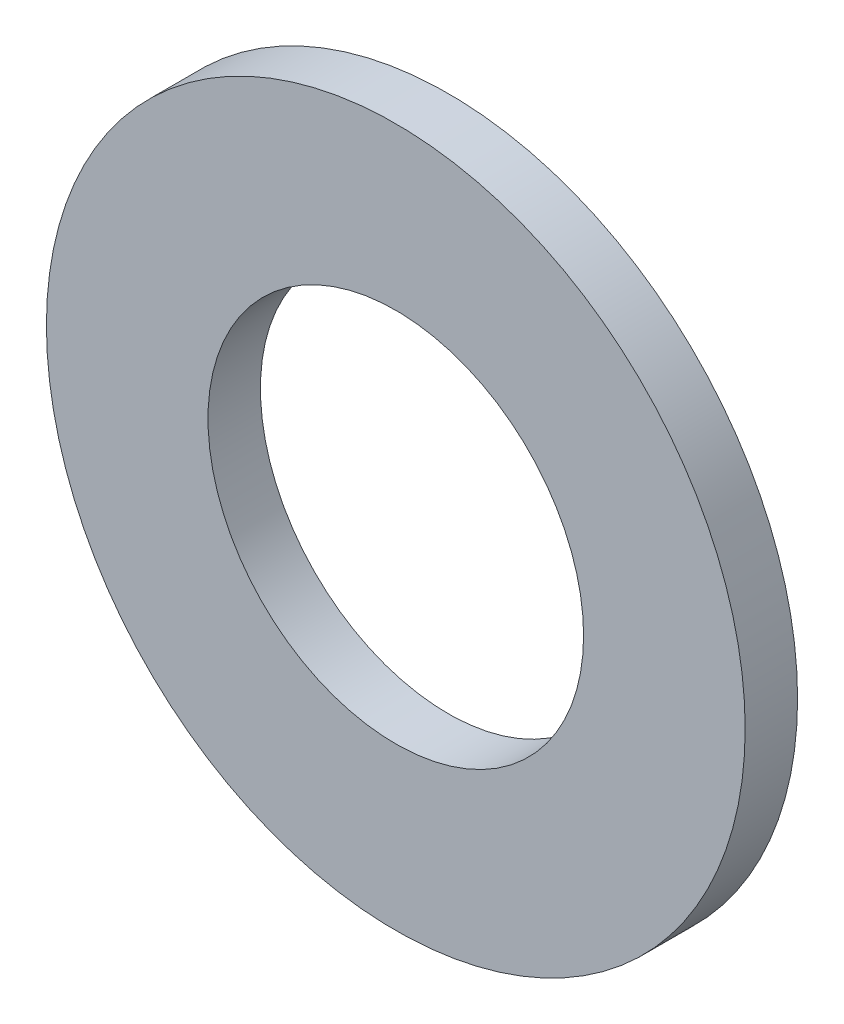
SolidWorks part; units mm, degrees
note: '?' marks a value the reader was unsure of.
ref_plane "Front Plane" through (0, 0, 0) normal (0, 0, 1) x (1, 0, 0)
ref_plane "Top Plane" through (0, 0, 0) normal (0, 1, 0) x (1, 0, 0)
ref_plane "Right Plane" through (0, 0, 0) normal (1, 0, 0) x (0, 0, -1)
sketch "Sketch1" plane through (0, 0, 0) normal (0, 0, 1) x (1, 0, 0)
  circle A0 centre (0, 0) radius 4
  circle A1 centre (0, 0) radius 2.15
  dimension "OD" = 8
  dimension "ID1" = 4.3
extrude "Boss-Extrude1" add sketch "Sketch1" along normal blind 0.6
ref_axis "Center Axis 1" through (0, 0, 0.6) along (0, 0, -1)?
ref_plane "Contact Plane 1" through (0, 0, 0.6) normal (0, 0, 1) x (1, 0, 0)
ref_plane "Contact Plane 2" through (0, 0, 0) normal (0, 0, -1) x (-1, 0, 0)
